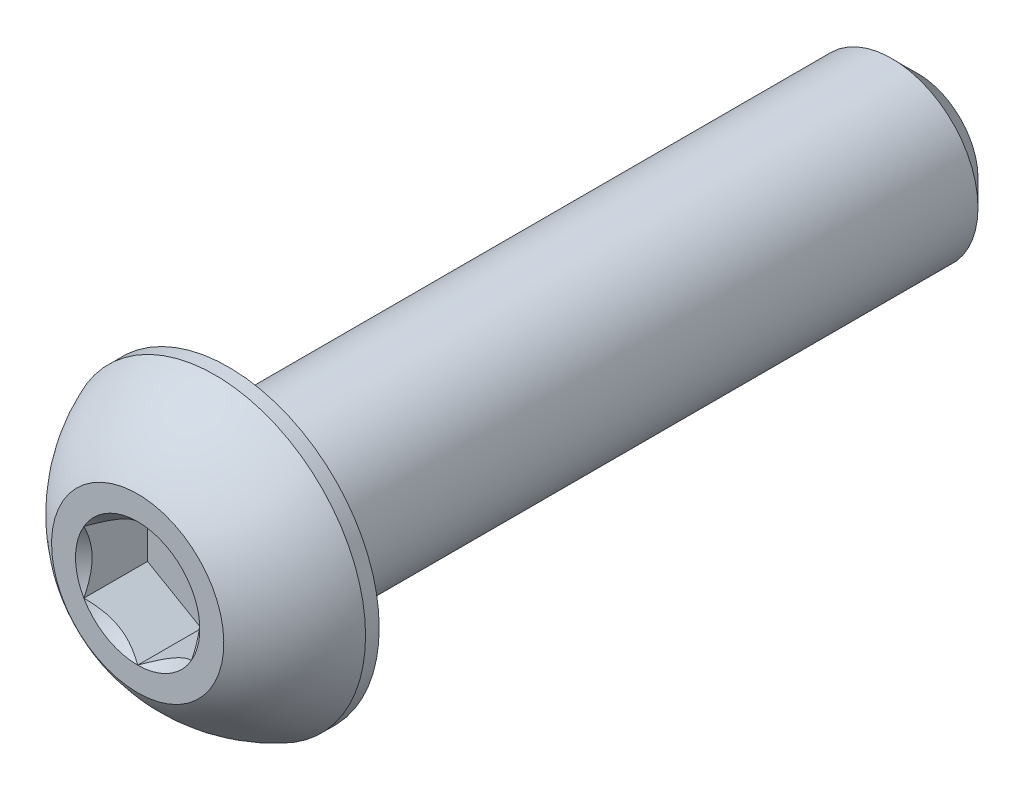
SolidWorks part; units mm, degrees
material "Alloy Steel"
ref_plane "Front" through (0, 0, 0) normal (0, 0, 1) x (1, 0, 0)
ref_plane "Top" through (0, 0, 0) normal (0, 1, 0) x (1, 0, 0)
ref_plane "Right" through (0, 0, 0) normal (1, 0, 0) x (0, 0, -1)
sketch "Sketch1" plane through (0, 0, 0) normal (1, 0, 0) x (0, 0, -1)
  line L2 (3.3528, 3.175) -> (28.7528, 3.175)
  line L3 (28.7528, 3.175) -> (28.7528, 0)
  line L4 (28.7528, 0) -> (3.3528, 0)
  line L6 (2.8499, 5.5499) -> (3.3528, 5.5499) construction
  line L7 (28.7528, 3.175) -> (28.7528, -3.175) construction
  line L8 (0, 0) -> (3.3528, 0) construction
  line L9 (3.3528, 5.5499) -> (3.3528, -5.5499) construction
  line L11 (3.3528, 3.175) -> (3.3528, 0)
  line L13 (0, 1.9844) -> (0, -1.9844) construction
  line L14 (0, 1.9844) -> (0, 3.175) construction
  arc A3 (0, 3.175) -> (2.8499, 5.5499) centre (5.0603, 0) cw construction
  dimension "D1" = 0.5029
revolve "Revolve1" add sketch "Sketch1" angle 360 mid plane about L4
sketch "Sketch3" plane through (0, 0, -28.7528) normal (0, 0, -1) x (-1, 0, 0)
  circle A0 centre (0, 0) radius 3.175
curve "Helix/Spiral1" pitch 1.27 height 26.67 turns 21
sketch "Sketch2" plane through (0, 0, 0) normal (1, 0, 0) x (0, 0, -1)
  line L0 (28.7528, 3.175) -> (29.864, 3.175)
  line L1 (29.864, 3.175) -> (29.3878, 2.3501)
  line L2 (29.3878, 2.3501) -> (29.229, 2.3501)
  line L3 (29.229, 2.3501) -> (28.7528, 3.175)
  line L4 (28.9909, 2.7626) -> (29.6259, 2.7626) construction
  dimension "D1" = 60
  dimension "D2" = 0.1588
  dimension "D3" = 0.635
chamfer "Chamfer1" distance 0.9525 angle 45 1 edges at (0, 3.175, -28.7528)
sweep "Cut-Sweep1" [suppressed] cut profiles "Sketch2" path "Helix/Spiral1"
sketch "Sketch7" plane through (0, 0, 0) normal (1, 0, 0) x (0, 0, -1)
  line L6 (2.8499, 5.5499) -> (3.3528, 5.5499) construction
  line L8 (0, 0) -> (3.3528, 0) construction
  line L11 (3.3528, 5.5499) -> (3.3528, -5.5499) construction
  line L12 (2.8499, 5.5499) -> (3.3528, 5.5499)
  line L13 (0, 0) -> (3.3528, 0)
  line L14 (0, 1.9844) -> (0, -1.9844) construction
  line L15 (3.3528, 5.5499) -> (3.3528, 0)
  line L16 (0, 3.175) -> (0, 0)
  arc A2 (2.8499, 5.5499) -> (0, 3.175) centre (5.0603, 0) ccw construction
  arc A3 (2.8499, 5.5499) -> (0, 3.175) centre (5.0603, 0) ccw
revolve "Revolve2" add sketch "Sketch7" angle 360 mid plane about L13
sketch "Sketch5" plane through (0, 0, 0) normal (0, 0, 1) x (1, 0, 0)
  line L1 (1.9844, -1.1457) -> (1.9844, 1.1457)
  line L2 (1.9844, 1.1457) -> (0, 2.2914)
  line L3 (0, 2.2914) -> (-1.9844, 1.1457)
  line L4 (-1.9844, 1.1457) -> (-1.9844, -1.1457)
  line L5 (-1.9844, -1.1457) -> (0, -2.2914)
  line L6 (0, -2.2914) -> (1.9844, -1.1457)
  circle A0 centre (0, 0) radius 1.9844 construction
extrude "Cut-Extrude2" cut sketch "Sketch5" against normal blind 2.347
sketch "Sketch6" plane through (0, 0, 0) normal (0, 0, 1) x (1, 0, 0)
  circle A0 centre (0, 0) radius 2.2914
extrude "Cut-Extrude3" cut sketch "Sketch6" against normal blind 2.347 draft 45
sketch "Sketch9" [suppressed] plane through (0, 0, -3.3528) normal (0, 0, 1) x (1, 0, 0)
  circle A2 centre (0, 0) radius 3.175
extrude "Boss-Extrude2" [suppressed] add sketch "Sketch9" against normal offset from surface (12.7 mm away) 22.225
sketch "Sketch10" plane through (0, 0, 0) normal (1, 0, 0) x (0, 0, -1)
  line L0 (28.7528, 3.175) -> (28.7528, -3.175) construction
  point P0 (26.8478, -3.175)
  dimension "D1" = 1.905
equation "\"D3@Helix/Spiral1\" = \"Lg@Sketch1\" + \"D4@Helix/Spiral1\""
equation "\"D2@Sketch2\" = \"D4@Helix/Spiral1\" * .125"
equation "\"D3@Sketch2\" = \"D4@Helix/Spiral1\" * .5"
equation "\"D1@Chamfer1\" = \"D4@Helix/Spiral1\" * .75"
equation "\"D1@Cut-Extrude2\" = \"Head Ht@Sketch1\" * .7"
equation "\"D1@Sketch1\" = \"Head Ht@Sketch1\" * .15"
equation "\"D1@Sketch10\" = \"D4@Helix/Spiral1\" * 1.5"
equation "\"D1@Cut-Extrude3\" = \"D1@Cut-Extrude2\""
